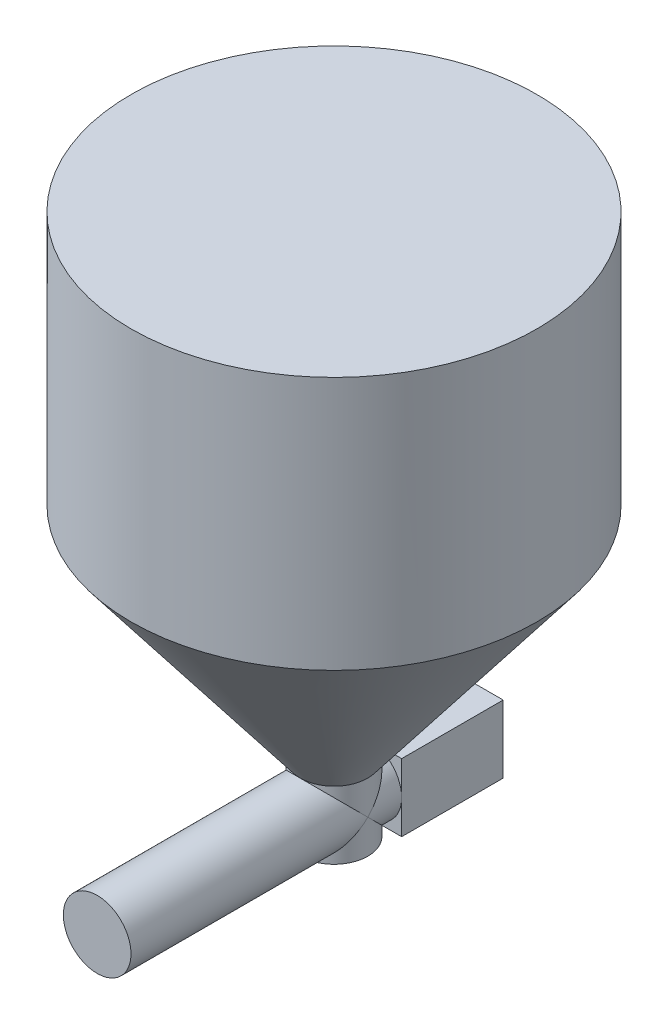
SolidWorks part; units mm, degrees
ref_plane "Alzado" through (0, 0, 0) normal (0, 0, 1) x (1, 0, 0)
ref_plane "Planta" through (0, 0, 0) normal (0, 1, 0) x (1, 0, 0)
ref_plane "Vista lateral" through (0, 0, 0) normal (1, 0, 0) x (0, 0, -1)
sketch "Croquis1" plane through (0, 0, 0) normal (0, 1, 0) x (1, 0, 0)
  circle A0 centre (0, 0) radius 300
  dimension "D1" = 600
ref_plane "Plano1" through (0, -700, 0) normal (0, 1, 0) x (1, 0, 0)
extrude "Saliente-Extruir1" add sketch "Croquis1" against normal blind 375 contours A0
sketch "Croquis2" plane through (0, -375, 0) normal (0, -1, 0) x (1, 0, 0)
  circle A0 centre (0, 0) radius 300
sketch "Croquis3" plane through (0, -700, 0) normal (0, 1, 0) x (1, 0, 0)
  circle A0 centre (0, 0) radius 50
  dimension "D1" = 100
loft "Recubrir1" add profiles "Croquis3", "Croquis2" connector at (-49.9253, -700, 2.7318) connector at (-299.408, -375, 18.8372)
sketch "Croquis4" plane through (0, -700, 0) normal (0, -1, 0) x (1, 0, 0)
  circle A0 centre (0, 0) radius 50
extrude "Saliente-Extruir2" add sketch "Croquis4" along normal blind 100
ref_plane "Plano2" through (0, 0, -50) normal (0, 0, -1) x (-1, 0, 0)
sketch "Croquis5" plane through (0, 0, -50) normal (0, 0, -1) x (-1, 0, 0)
  line L0 (-50, -800) -> (50, -800) construction
  line L3 (0, -800) -> (0, -700) construction
  line L4 (330, -700) -> (-330, -700) construction
  circle A0 centre (0, -750) radius 50
extrude "Saliente-Extruir3" add sketch "Croquis5" against normal blind 400
sketch "Croquis6" plane through (0, 0, -50) normal (0, 0, -1) x (-1, 0, 0)
  line L0 (-50, -750) -> (50, -750) construction
  line L2 (-50, -700) -> (50, -700)
  line L3 (-50, -700) -> (-50, -800)
  line L4 (-50, -800) -> (50, -800)
  line L5 (50, -700) -> (50, -800)
  line L6 (-50, -700) -> (50, -800) construction
  line L7 (-50, -800) -> (50, -700) construction
  arc A0 (0, -700) -> (0, -800) centre (0, -750) ccw construction
  arc A1 (0, -800) -> (0, -700) centre (0, -750) ccw construction
  point P8 (0, -750)
  dimension "D1" = 100
  dimension "D2" = 100
extrude "Saliente-Extruir4" add sketch "Croquis6" along normal blind 150
